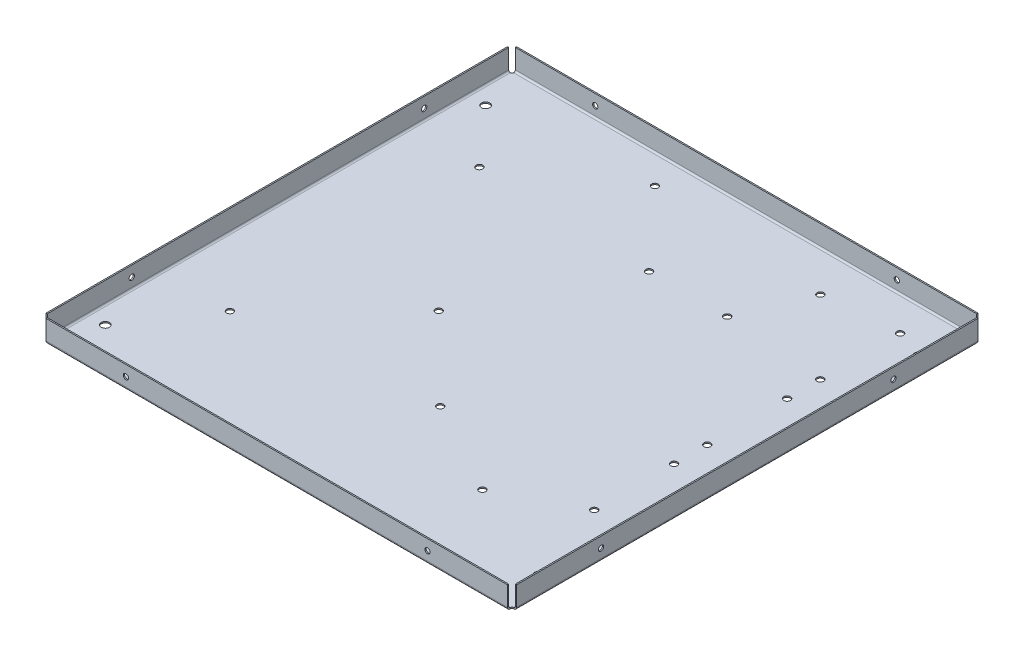
SolidWorks part; units mm, degrees
note: The reader was unsure of these and kept them because the rebuilt part matched: flange length of "Edge-Flange1".
ref_plane "Front Plane" through (0, 0, 0) normal (0, 0, 1) x (1, 0, 0)
ref_plane "Top Plane" through (0, 0, 0) normal (0, 1, 0) x (1, 0, 0)
ref_plane "Right Plane" through (0, 0, 0) normal (1, 0, 0) x (0, 0, -1)
sketch "Sketch1" plane through (0, 0, 0) normal (0, 1, 0) x (1, 0, 0)
  line L1 (0, 0) -> (279.4, 0)
  line L2 (0, 0) -> (0, 279.4)
  line L3 (0, 279.4) -> (279.4, 279.4)
  line L4 (279.4, 0) -> (279.4, 279.4)
  dimension "D1" = 279.4
  dimension "D2" = 279.4
sheet metal parameters "Sheet-Metal1" thickness 0.7595 parameters "D1"=6.35
base flange "Base-Flange1" sketch "Sketch1" thickness 0.7595 reverse thickness direction yes parameters "D1"=6.35
sketch "Sketch4" plane through (0, 0.7595, 0) normal (0, 1, 0) x (1, 0, 0)
  line L0 (279.4, 0) -> (279.4, 279.4) construction
  circle A0 centre (0, 0) radius 1
  circle A1 centre (0, 279.4) radius 1
  circle A2 centre (279.4, 279.4) radius 1
  circle A3 centre (279.4, 0) radius 1
  dimension "D1" = 2
extrude "Cut-Extrude1" cut sketch "Sketch4" against normal through all normal cut yes
edge flange "Edge-Flange1" sketch "Sketch13" flange profiles "Sketch13", "Sketch14", "Sketch15", "Sketch16" flange angle 90 flange length 12.7 flange position bend outside bend radius 1 thickness 0.7595 relief rectangular gap distance 1 parameters "D6"=10, "D8"=1
sketch "Sketch13" plane through (0, 0.7595, -279.4) normal (0, 0, -1) x (-1, 0, 0)
  line L2 (-278.4, 0) -> (-278.4, 12.7)
  line L3 (-278.4, 12.7) -> (-1, 12.7)
  line L4 (-1, 12.7) -> (-1, 0)
  line L5 (-278.4, 0) -> (-1, 0) construction
  line L6 (-278.4, 0) -> (-1, 0)
sketch "Sketch14" plane through (0, 0.7595, 0) normal (-1, 0, 0) x (0, 0, 1)
  line L0 (-278.4, 0) -> (-1, 0) construction
  line L1 (-278.4, 0) -> (-1, 0)
  line L2 (-278.4, 0) -> (-278.4, 12.7)
  line L3 (-278.4, 12.7) -> (-1, 12.7)
  line L4 (-1, 12.7) -> (-1, 0)
sketch "Sketch15" plane through (0, 0.7595, 0) normal (0, 0, 1) x (1, 0, 0)
  line L0 (1, 0) -> (278.4, 0) construction
  line L1 (1, 0) -> (278.4, 0)
  line L2 (1, 0) -> (1, 12.7)
  line L3 (1, 12.7) -> (278.4, 12.7)
  line L4 (278.4, 12.7) -> (278.4, 0)
sketch "Sketch16" plane through (279.4, 0.7595, 0) normal (1, 0, 0) x (0, 0, -1)
  line L0 (1, 0) -> (278.4, 0) construction
  line L1 (1, 0) -> (278.4, 0)
  line L2 (1, 0) -> (1, 12.7)
  line L3 (1, 12.7) -> (278.4, 12.7)
  line L4 (278.4, 12.7) -> (278.4, 0)
bend "EdgeBend1" bend radius 1 bend angle 90 parameters "D5"=1
bend "EdgeBend2" bend radius 1 bend angle 90 parameters "D5"=2
bend "EdgeBend3" bend radius 1 bend angle 90 parameters "D5"=3
bend "EdgeBend4" bend radius 1 bend angle 90 parameters "D5"=4
sketch "Sketch17" plane through (0, 0.7595, 0) normal (0, 1, 0) x (1, 0, 0)
  line L0 (0, 278.4) -> (0, 1) construction
  line L1 (278.4, 279.4) -> (1, 279.4) construction
  line L3 (9.525, 254) -> (269.875, 254) construction
  line L4 (9.525, 254) -> (9.525, 25.4) construction
  line L5 (9.525, 25.4) -> (269.875, 25.4) construction
  line L6 (269.875, 254) -> (269.875, 25.4) construction
  line L7 (9.525, 25.4) -> (9.525, 0) construction
  line L8 (1, 0) -> (278.4, 0) construction
  line L9 (269.875, 25.4) -> (279.4, 25.4) construction
  line L10 (279.4, 1) -> (279.4, 278.4) construction
  line L11 (9.525, 25.4) -> (0, 25.4) construction
  line L13 (9.525, 254) -> (9.525, 279.4) construction
  circle A0 centre (9.525, 254) radius 2.5
  circle A1 centre (269.875, 254) radius 2.5
  circle A2 centre (269.875, 25.4) radius 2.5
  circle A3 centre (9.525, 25.4) radius 2.5
  dimension "D1" = 5
  dimension "D2" = 9.525
  dimension "D3" = 25.4
extrude "Cut-Extrude2" cut sketch "Sketch17" against normal up to next normal cut yes
sketch "Sketch18" plane through (0, 0.7595, 0) normal (0, 1, 0) x (1, 0, 0)
  line L0 (269.875, 254) -> (269.875, 25.4) construction
  line L1 (9.525, 254) -> (9.525, 25.4) construction
sketch "Sketch19" plane through (0, 0.7595, 0) normal (0, 1, 0) x (1, 0, 0)
  circle A0 centre (252.8405, 259.9) radius 2
  circle A1 centre (252.8405, 211.9) radius 2
  circle A2 centre (252.8405, 191.95) radius 2
  circle A3 centre (252.8405, 143.95) radius 2
  circle A4 centre (252.8405, 124) radius 2
  circle A5 centre (252.8405, 76) radius 2
  circle A6 centre (252.8405, 259.9) radius 2 construction
extrude "Cut-Extrude3" cut sketch "Sketch19" against normal through all normal cut yes
sketch "Sketch20" plane through (0, 0.7595, 0) normal (0, 1, 0) x (1, 0, 0)
  line L0 (278.4, 279.4) -> (1, 279.4) construction
  line L1 (0, 278.4) -> (0, 1) construction
  circle A0 centre (102.4, 262.94) radius 2
  circle A1 centre (102.4, 132.94) radius 2
  circle A2 centre (39.81, 220) radius 2
  circle A3 centre (39.81, 70) radius 2
  circle A4 centre (152.58, 83.7) radius 2
  circle A5 centre (192.1, 216.7) radius 2
  circle A6 centre (145.1, 216.7) radius 2
  circle A7 centre (208.68, 256.14) radius 2
  circle A8 centre (208.68, 52.94) radius 2
  dimension "D1" = 4
  dimension "D5" = 152.58
  dimension "D2" = 16.46
  dimension "D3" = 130
  dimension "D4" = 102.4
  dimension "D6" = 195.7
  dimension "D7" = 150
  dimension "D8" = 59.4
  dimension "D9" = 39.81
  dimension "D10" = 62.7
  dimension "D11" = 47
  dimension "D12" = 145.1
  dimension "D13" = 23.26
  dimension "D14" = 203.2
  dimension "D15" = 208.68
extrude "Cut-Extrude4" cut sketch "Sketch20" against normal through all normal cut yes
sketch "Sketch22" plane through (0, 0, 1.7595) normal (0, 0, 1) x (1, 0, 0)
  line L1 (281.1595, 13.4595) -> (281.1595, 1.7595) construction
  line L2 (230.3595, 7.1095) -> (278.4, 7.1095) construction
  line L4 (49.0405, 7.1095) -> (1, 7.1095) construction
  line L6 (1, 13.4595) -> (1, 1.7595) construction
  line L7 (278.4, 1.7595) -> (278.4, 13.4595) construction
  line L8 (278.4, 13.4595) -> (1, 13.4595) construction
  circle A0 centre (49.0405, 7.1095) radius 1.5875
  circle A1 centre (230.3595, 7.1095) radius 1.5875
  dimension "D1" = 3.175
  dimension "D2" = 50.8
  dimension "D3" = 6.35
extrude "Cut-Extrude5" cut sketch "Sketch22" against normal through all normal cut yes
sketch "Sketch23" plane through (-1.7595, 0, 0) normal (-1, 0, 0) x (0, 0, 1)
  line L0 (-278.4, 7.1095) -> (-227.6, 7.1095) construction
  line L1 (-278.4, 13.4595) -> (-278.4, 1.7595) construction
  line L2 (-227.6, 7.1095) -> (-51.8, 7.1095) construction
  line L3 (-51.8, 7.1095) -> (-1, 7.1095) construction
  line L4 (-1, 1.7595) -> (-1, 13.4595) construction
  line L5 (-1, 13.4595) -> (-278.4, 13.4595) construction
  circle A0 centre (-227.6, 7.1095) radius 1.5875
  circle A1 centre (-51.8, 7.1095) radius 1.5875
  dimension "D2" = 3.175
  dimension "D1" = 6.35
  dimension "D3" = 50.8
extrude "Cut-Extrude6" cut sketch "Sketch23" against normal through all normal cut yes
flat pattern "Flat-Pattern1" [suppressed]
sketch "Bend-Lines1" plane through (0, 0, 0) normal (0, -1, 0) x (-1, 0, 0)
  line L0 (-280.4836, 278.4) -> (-280.4836, 1) construction
  line L1 (-278.4, -1.0836) -> (-1, -1.0836) construction
  line L2 (1.0836, 1) -> (1.0836, 278.4) construction
  line L3 (-1, 280.4836) -> (-278.4, 280.4836) construction
  line L4 (-280.4836, 278.4) -> (-280.4836, 1) construction
  line L5 (-278.4, -1.0836) -> (-1, -1.0836) construction
  line L6 (1.0836, 1) -> (1.0836, 278.4) construction
  line L7 (-1, 280.4836) -> (-278.4, 280.4836) construction
sketch3d "Bounding-Box1" [suppressed]
  line L0 (13.8673, -13.8673, 0) -> (13.8673, 293.2673, 0) construction
  line L1 (-293.2673, -13.8673, 0) -> (-293.2673, 293.2673, 0) construction
  line L2 (13.8673, -13.8673, 0) -> (-293.2673, -13.8673, 0) construction
  line L3 (13.8673, 293.2673, 0) -> (-293.2673, 293.2673, 0) construction
bend of the flat pattern "Flatten-<EdgeBend1>1"
bend of the flat pattern "Flatten-<EdgeBend2>1"
bend of the flat pattern "Flatten-<EdgeBend3>1"
bend of the flat pattern "Flatten-<EdgeBend4>1"
